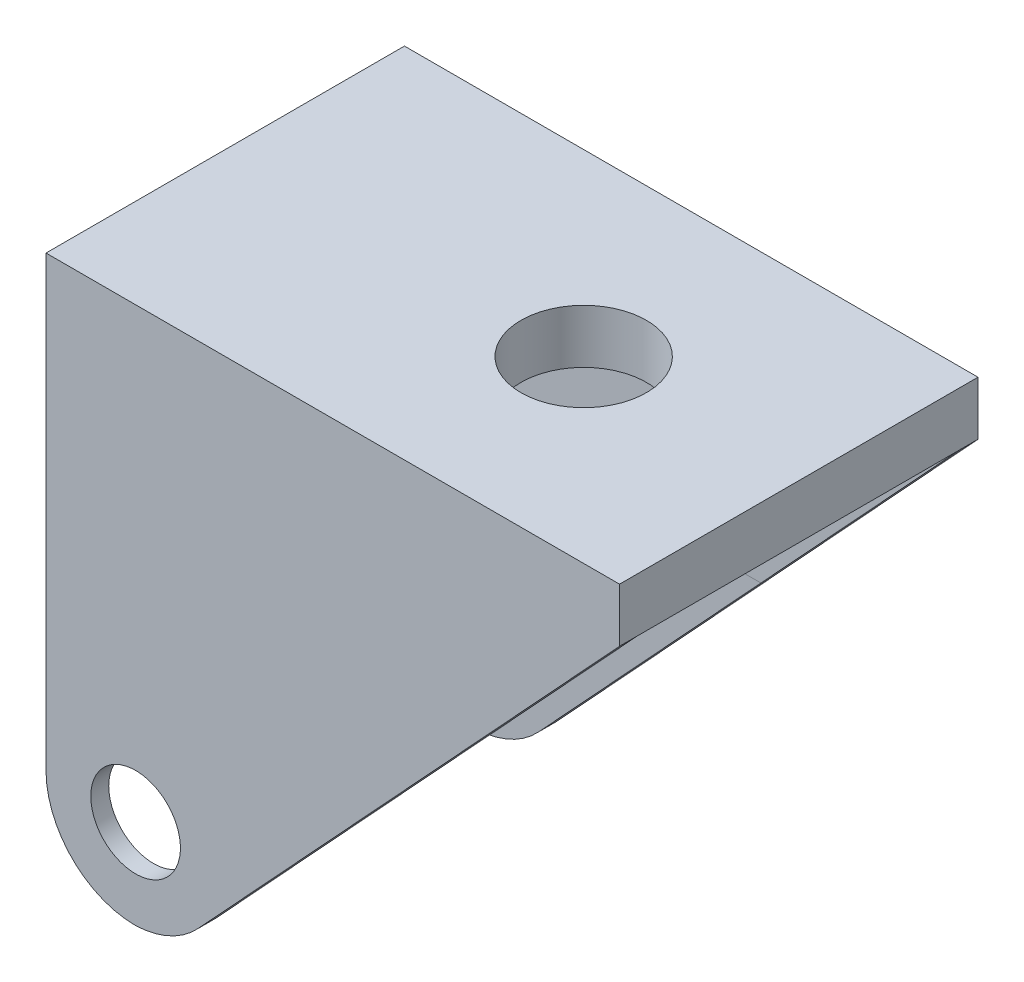
SolidWorks part; units mm, degrees
ref_plane "Front Plane" through (0, 0, 0) normal (0, 0, 1) x (1, 0, 0)
ref_plane "Top Plane" through (0, 0, 0) normal (0, 1, 0) x (1, 0, 0)
ref_plane "Right Plane" through (0, 0, 0) normal (1, 0, 0) x (0, 0, -1)
sketch "Sketch4" plane through (0, 0, 0) normal (1, 0, 0) x (0, 0, -1)
  line L1 (10, -15) -> (-10, -15)
  line L2 (10, -15) -> (10, 15)
  line L3 (10, 15) -> (-10, 15)
  line L4 (-10, -15) -> (-10, 15)
  line L5 (10, -15) -> (-10, 15) construction
  line L6 (10, 15) -> (-10, -15) construction
  point P0 (0, 0)
  dimension "D1" = 20
  dimension "D2" = 30
extrude "Boss-Extrude2" add sketch "Sketch4" along normal mid plane 32
sketch "Sketch5" plane through (-16, 0, 0) normal (-1, 0, 0) x (0, 0, 1)
  line L0 (-9, 0) -> (-9, 12)
  line L5 (-9, 12) -> (9, 12)
  line L6 (9, 12) -> (9, 0)
  line L7 (10, 15) -> (10, -15) construction
  line L9 (-10, -15) -> (-10, 15) construction
  line L10 (-10, 15) -> (10, 15) construction
  line L11 (9, 0) -> (9, -15)
  line L12 (10, -15) -> (-10, -15) construction
  line L13 (-9, 0) -> (-9, -15)
  point P0 (0, 0)
  dimension "D1" = 1
  dimension "D2" = 1
  dimension "D3" = 3
extrude "Cut-Extrude2" cut sketch "Sketch5" against normal blind 32 and the other way through all flip side to cut
sketch "Sketch6" plane through (0, 0, -10) normal (0, 0, -1) x (-1, 0, 0)
  line L0 (16, -15) -> (9, -15) construction
  line L1 (-16, -15) -> (16, -15) construction
  line L2 (-16, 15) -> (-16, 12) construction
  line L3 (-16, -15) -> (-16, 15) construction
  line L4 (-16, 12) -> (9, -15)
  dimension "D1" = 7
  dimension "D2" = 3
extrude "Cut-Extrude4" cut sketch "Sketch6" against normal through all and the other way through all flip side to cut
sketch "Sketch7" plane through (0, 0, -10) normal (0, 0, -1) x (-1, 0, 0)
  line L0 (16, 15) -> (11, 15) construction
  line L1 (-16, 15) -> (16, 15) construction
  line L2 (11, 15) -> (11, -10) construction
  circle A0 centre (11, -10) radius 2.5
  dimension "D1" = 5
  dimension "D2" = 25
extrude "Cut-Extrude5" cut sketch "Sketch7" against normal through all
fillet "Fillet2" radius 5 1 edges at (-16, -15, -9.5)
fillet "Fillet3" radius 5 1 edges at (-9, -15, -9.5)
fillet "Fillet4" radius 5 1 edges at (-16, -15, 9.5)
fillet "Fillet5" radius 5 1 edges at (-9, -15, 9.5)
sketch "Sketch8" plane through (0, 15, 0) normal (0, 1, 0) x (1, 0, 0)
  line L0 (16, 0) -> (4, 0) construction
  line L1 (16, 10) -> (16, -10) construction
  circle A0 centre (4, 0) radius 3.5
  dimension "D1" = 12
extrude "Cut-Extrude6" cut sketch "Sketch8" against normal up to next
